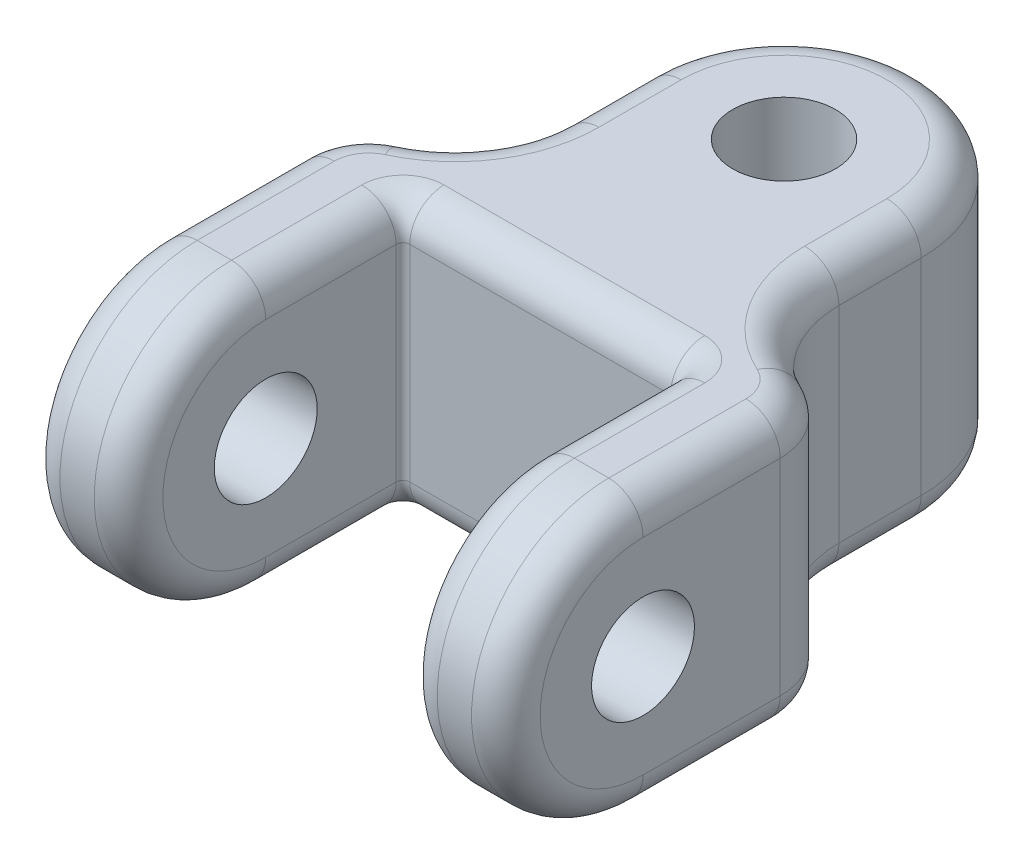
SolidWorks part; units mm, degrees
ref_plane "Front Plane" through (0, 0, 0) normal (0, 0, 1) x (1, 0, 0)
ref_plane "Top Plane" through (0, 0, 0) normal (0, 1, 0) x (1, 0, 0)
ref_plane "Right Plane" through (0, 0, 0) normal (1, 0, 0) x (0, 0, -1)
sketch "Sketch1" plane through (0, 0, 0) normal (0, 1, 0) x (1, 0, 0)
  line L0 (-20, 40) -> (-20, 0)
  line L1 (-20, 0) -> (-35, 0)
  line L2 (-35, 0) -> (-35, 40)
  line L3 (-20, 63.5584) -> (-20, 75.5584)
  line L4 (0, 0) -> (0, 48.687) construction
  line L5 (20, 0) -> (35, 0)
  line L6 (35, 0) -> (35, 40)
  line L7 (20, 63.5584) -> (20, 75.5584)
  line L8 (20, 40) -> (20, 0)
  line L9 (-20, 40) -> (20, 40)
  arc A0 (-35, 40) -> (-29.2308, 49.0609) centre (-25, 40) cw
  arc A1 (-29.2308, 49.0609) -> (-20, 63.5584) centre (-36, 63.5584) ccw
  arc A2 (-20, 75.5584) -> (20, 75.5584) centre (0, 75.5584) cw
  arc A3 (35, 40) -> (29.2308, 49.0609) centre (25, 40) ccw
  arc A4 (29.2308, 49.0609) -> (20, 63.5584) centre (36, 63.5584) cw
  dimension "D5" = 10
  dimension "D6" = 16
  dimension "D8" = 20
  dimension "D1" = 20
  dimension "D2" = 15
  dimension "D3" = 40
  dimension "D4" = 40
  dimension "D7" = 12
extrude "Boss-Extrude1" add sketch "Sketch1" along normal mid plane 40
fillet "Fillet1" 2 edges at (-27.5, 20, 0) (-27.5, -20, 0) type full round first side face at (0, 20, -39.6677) second side face at (0, -20, -39.6677) middle face at (-27.5, 0, 0)
fillet "Fillet2" 2 edges at (27.5, 20, 0) (27.5, -20, 0) type full round first side face at (0, 20, -42.5248) second side face at (0, -20, -42.5248) middle face at (27.5, 0, 0)
sketch "Sketch2" plane through (35, 0, 0) normal (1, 0, 0) x (0, 0, -1)
  circle A0 centre (20, 0) radius 7.5
  dimension "D1" = 15
extrude "Cut-Extrude1" cut sketch "Sketch2" against normal through all
sketch "Sketch3" plane through (0, 20, 0) normal (0, 1, 0) x (1, 0, 0)
  circle A0 centre (0, 75.5584) radius 7.5
  dimension "D1" = 15
extrude "Cut-Extrude2" cut sketch "Sketch3" against normal through all
fillet "Fillet3" radius 1 2 edges at (20, 0, -40) (-20, 0, -40)
fillet "Fillet4" radius 5 32 edges at (-35, -20, -30) (-33.4353, -20, -45.3709) (-22.5036, -20, -54.9651) (-20, -20, -69.5584) (0, -20, -95.5584) (20, -20, -69.5584) (22.5036, -20, -54.9651) (33.4353, -20, -45.3709) (35, -20, -30) (35, 0, 0) (35, 20, -30) (33.4353, 20, -45.3709) (22.5036, 20, -54.9651) (20, 20, -69.5584) (0, 20, -95.5584) (-20, 20, -69.5584) (-22.5036, 20, -54.9651) (-33.4353, 20, -45.3709) (-35, 20, -30) (-20, 20, -29.5) (-19.7071, 20, -39.7071) (0, 20, -40) (19.7071, 20, -39.7071) (20, 20, -29.5) (20, 0, 0) (20, -20, -29.5) (19.7071, -20, -39.7071) (0, -20, -40) (-19.7071, -20, -39.7071) (-20, -20, -29.5) (-35, 0, 0) (-20, 0, 0)
